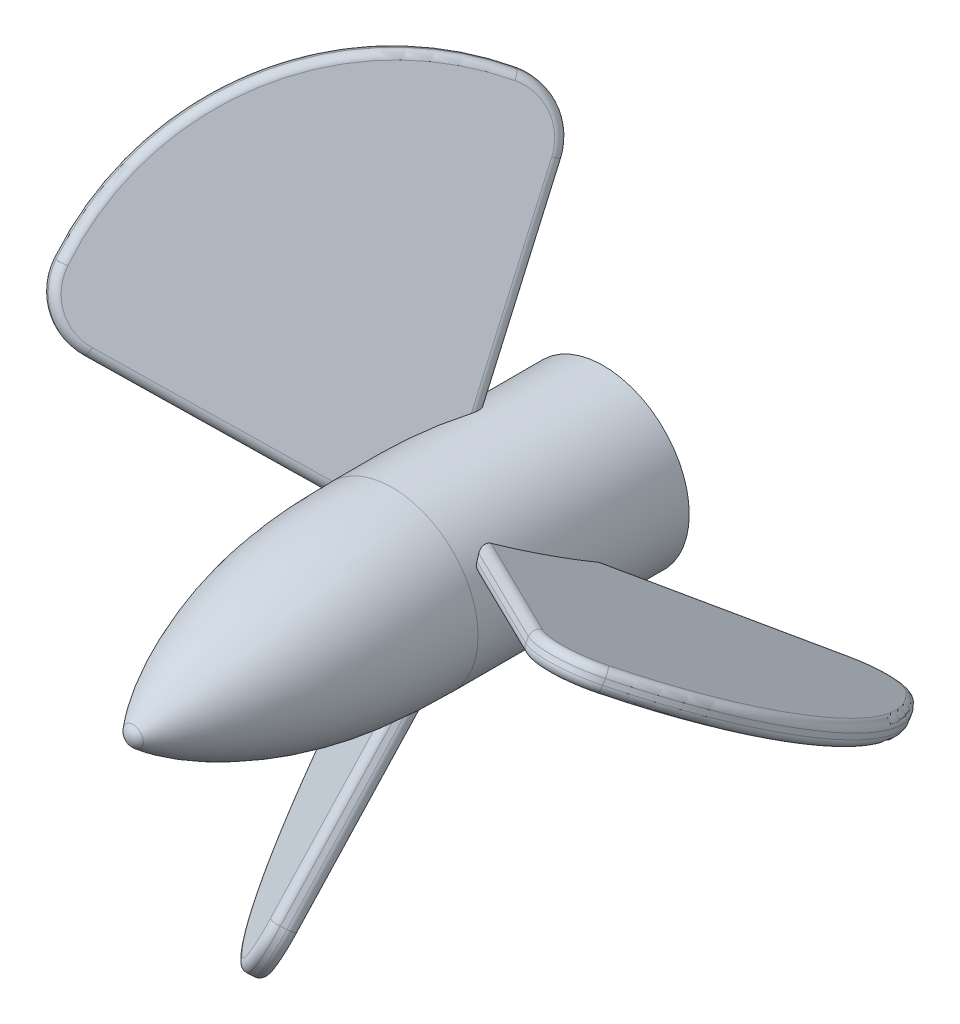
SolidWorks part; units mm, degrees
ref_plane "Front Plane" through (0, 0, 0) normal (0, 0, 1) x (1, 0, 0)
ref_plane "Top Plane" through (0, 0, 0) normal (0, 1, 0) x (1, 0, 0)
ref_plane "Right Plane" through (0, 0, 0) normal (1, 0, 0) x (0, 0, -1)
sketch "Sketch1" plane through (0, 0, 0) normal (0, 0, 1) x (1, 0, 0)
  circle A0 centre (0, 0) radius 3.25
  dimension "D1" = 6.5
extrude "Boss-Extrude1" add sketch "Sketch1" along normal mid plane 8
ref_plane "Plane1" through (12, 0, 0) normal (1, 0, 0) x (0, 0, -1)
ref_axis "Axis1" through (2.75, 0, 0) along (-1, 0, 0)
ref_plane "Plane2" through (0, 0, 0) normal (0, 0.866, -0.5) x (-1, 0, 0)
sketch "Sketch6" plane through (0, 0, 0) normal (0, 0.866, -0.5) x (-1, 0, 0)
  line L0 (0, 1.8) -> (-10, 9.8)
  line L1 (0, 1.8) -> (-10, -6.2)
  arc A0 (-10, -6.2) -> (-10, 9.8) centre (-4, 1.8) cw
  point P4 (0, 1.7471)
  dimension "D4" = 10
  dimension "D1" = 16
  dimension "D2" = 10
  dimension "D3" = 8
extrude "Boss-Extrude4" add sketch "Sketch6" along normal mid plane 0.8
fillet "Fillet1" radius 2 2 edges at (10, -3.1, -5.3694) (10, 4.9, 8.487)
pattern_circular "CirPattern2" count 3 over 360 about axis through (0, 0, 4) along (0, 0, -1) of "Boss-Extrude4", "Fillet1"
sketch "Sketch7" plane through (0, 0, 4) normal (0, 0, 1) x (1, 0, 0)
  line L0 (2.2913, 1) -> (1, 1)
  line L1 (2.2913, -1) -> (1, -1)
  line L2 (1, 2.2913) -> (1, 1)
  line L3 (-1, 2.2913) -> (-1, 1)
  line L4 (1, -1) -> (1, -2.2913)
  line L5 (-1, 1) -> (-2.2913, 1)
  line L6 (-1, -1) -> (-1, -2.2913)
  line L7 (-1, -1) -> (-2.2913, -1)
  arc A1 (1, 2.2913) -> (-1, 2.2913) centre (0, 0) ccw
  arc A2 (-2.2913, 1) -> (-2.2913, -1) centre (0, 0) ccw
  arc A3 (2.2913, -1) -> (2.2913, 1) centre (0, 0) ccw
  arc A4 (-1, -2.2913) -> (1, -2.2913) centre (0, 0) ccw
  dimension "D1" = 5
  dimension "D2" = 1
  dimension "D3" = 2
  dimension "D4" = 1
  dimension "D5" = 2
extrude "Cut-Extrude1" cut sketch "Sketch7" against normal up to next
fillet "Fillet2" radius 0.3 30 edges at (-0.4008, -6.3865, 5.7296) (-1.3698, -10.8508, 8.1423) (-6.5206, -12.4012, 1.7588) (-7.7533, -7.1653, -4.6246) (0.2298, -6.5203, 5.1915) (-0.7698, -11.1972, 7.7423) (-5.9206, -12.7476, 1.3588) (-7.1533, -7.5117, -5.0246) (-5.7617, 3.0612, 5.1915) (-9.3121, 6.2653, 7.7423) (-8.0794, 11.5012, 1.3588) (-1.9951, 5.7321, -2.7715) (-1.389, 6.0364, -2.3441) (-5.3304, 3.5404, 5.7296) (-8.7121, 6.6117, 8.1423) (-7.4794, 11.8476, 1.7588) (5.9221, -1.8153, -2.3441) (10.082, -3.1319, -4.6246) (14, 0.5536, 1.7588) (10.082, 4.2391, 8.1423) (5.9617, -1.1383, -2.7715) (10.082, -2.4391, -5.0246) (14, 1.2464, 1.3588) (10.082, 4.9319, 7.7423) (-4.5331, -4.2211, -2.3441) (-3.9666, -4.5938, -2.7715) (-2.9287, 9.9508, -5.0246) (-2.3287, 10.2972, -4.6246) (5.7313, 2.8461, 5.7296) (5.5319, 3.4592, 5.1915)
sketch "Sketch8" plane through (0, 0, 0) normal (1, 0, 0) x (0, 0, -1)
  line L0 (-4, 3.25) -> (-4, 0)
  line L1 (-4, 3.25) -> (-4, -3.25) construction
  line L2 (-4, 0) -> (-14, 0)
  line L3 (4, 3.25) -> (-4, 3.25) construction
  arc A0 (-13.8207, 0.3836) -> (-14, 0) centre (-13.5, 0) ccw
  spline S0 degree 3 poles (-4, 3.25) (-6.4474, 3.25) (-9.5268, 2.856) (-12.9132, 1.1423) (-13.8207, 0.3836) knots 0 0 0 0 0.632395 0.948754 0.948754 0.948754 0.948754
  dimension "D2" = 1
  dimension "D1" = 10
revolve "Revolve1" add sketch "Sketch8" angle 360 about L2
